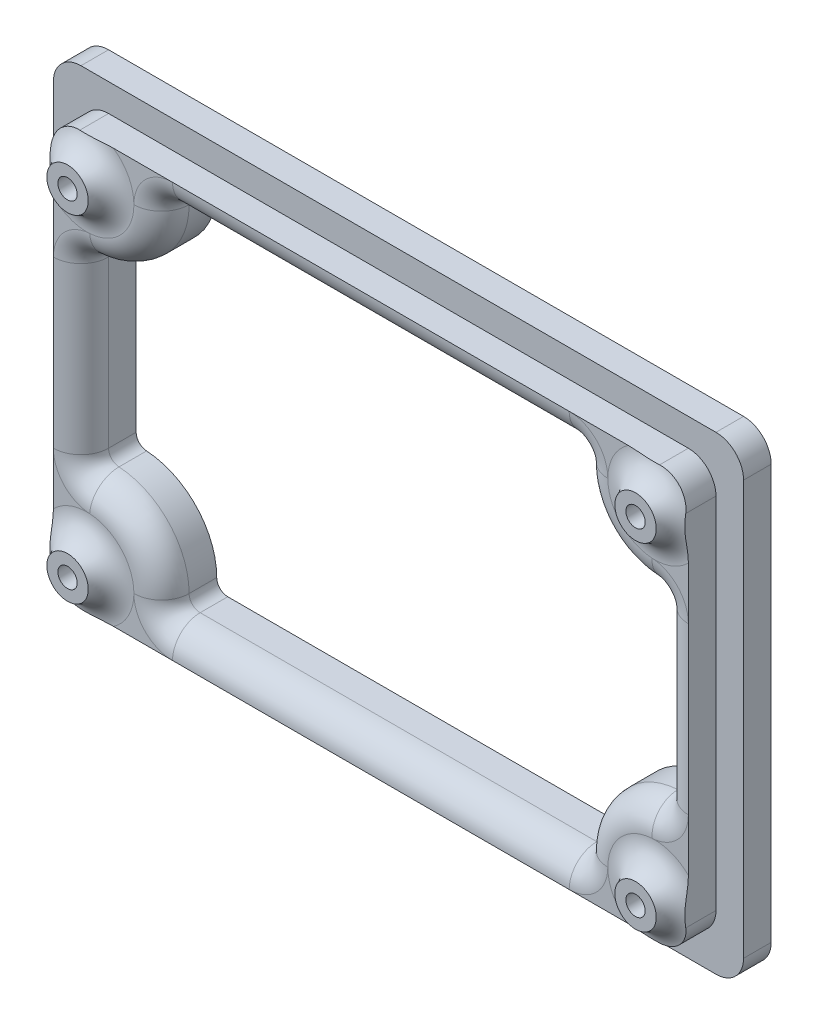
SolidWorks part; units mm, degrees
ref_plane "Ebene vorne" through (0, 0, 0) normal (0, 0, 1) x (1, 0, 0)
ref_plane "Ebene oben" through (0, 0, 0) normal (0, 1, 0) x (1, 0, 0)
ref_plane "Ebene rechts" through (0, 0, 0) normal (1, 0, 0) x (0, 0, -1)
sketch "Skizze1" plane through (0, 0, 0) normal (0, 0, 1) x (1, 0, 0)
  line L0 (-57.5, 75) -> (-57.5, 0) construction
  line L1 (0, 0) -> (-115, 0)
  line L2 (0, 0) -> (0, 75)
  line L3 (0, 75) -> (-115, 75)
  line L4 (-115, 0) -> (-115, 75)
  line L5 (-115, 37.5) -> (0, 37.5) construction
  circle A0 centre (-108.935, 67.98) radius 1.75
  circle A1 centre (-6.065, 67.98) radius 1.75
  circle A2 centre (-6.065, 7.02) radius 1.75
  circle A3 centre (-108.935, 7.02) radius 1.75
  dimension "D3" = 3.5
  dimension "D1" = 75
  dimension "D2" = 115
  dimension "D4" = 102.87
  dimension "D5" = 60.96
extrude "Aufsatz-Linear austragen1" add sketch "Skizze1" along normal blind 5
sketch "Skizze2" plane through (0, 0, 5) normal (0, 0, 1) x (1, 0, 0)
  line L0 (-57.5, 75) -> (-57.5, 0) construction
  line L1 (0, 75) -> (-115, 75) construction
  line L2 (-115, 0) -> (0, 0) construction
  line L3 (-115, 37.5) -> (0, 37.5) construction
  line L4 (-115, 75) -> (-115, 0) construction
  line L5 (0, 0) -> (0, 75) construction
  circle A11 centre (-108.935, 67.98) radius 1.75 construction
  circle A12 centre (-108.935, 67.98) radius 3.75
  circle A13 centre (-108.935, 67.98) radius 3.75
  circle A14 centre (-108.935, 67.98) radius 1.75
  circle A15 centre (-6.065, 67.98) radius 1.75
  circle A16 centre (-6.065, 67.98) radius 3.75
  circle A17 centre (-108.935, 7.02) radius 1.75
  circle A18 centre (-108.935, 7.02) radius 3.75
  circle A19 centre (-6.065, 7.02) radius 3.75
  circle A20 centre (-6.065, 7.02) radius 1.75
  dimension "D1" = 2
extrude "Aufsatz-Linear austragen2" add sketch "Skizze2" along normal blind 3.5
sketch "Skizze3" plane through (0, 0, 0) normal (0, 0, -1) x (-1, 0, 0)
  line L24 (-5, 80) -> (-5, -5)
  line L25 (-5, -5) -> (120, -5)
  line L30 (120, -5) -> (120, 80)
  line L31 (120, 80) -> (-5, 80)
  line L32 (-5, 80) -> (-5, -5)
  line L33 (-5, -5) -> (120, -5)
  line L34 (120, -5) -> (120, 80)
  line L35 (120, 80) -> (-5, 80)
  dimension "D1" = 5
extrude "Aufsatz-Linear austragen4" add sketch "Skizze3" along normal blind 5 contours L32 L33 L34 L35
fillet "Verrundung1" radius 5 4 edges at (-115, 75, 2.5) (-115, 0, 2.5) (0, 0, 2.5) (0, 75, 2.5)
fillet "Verrundung2" radius 5 4 edges at (5, -5, -2.5) (5, 80, -2.5) (-120, 80, -2.5) (-120, -5, -2.5)
fillet "Verrundung3" radius 5 4 edges at (-105.185, 67.98, 5) (-9.815, 67.98, 5) (-2.315, 7.02, 5) (-112.685, 7.02, 5)
sketch "Skizze4" plane through (0, 0, 8.5) normal (0, 0, 1) x (1, 0, 0)
  circle A0 centre (-108.935, 7.02) radius 1.75 construction
  circle A1 centre (-6.065, 7.02) radius 1.75 construction
  circle A2 centre (-6.065, 67.98) radius 1.75 construction
  circle A3 centre (-108.935, 67.98) radius 1.75 construction
  circle A4 centre (-108.935, 7.02) radius 1.75
  circle A5 centre (-6.065, 7.02) radius 1.75
  circle A6 centre (-6.065, 67.98) radius 1.75
  circle A7 centre (-108.935, 67.98) radius 1.75
extrude "Schnitt-Linear austragen1" cut sketch "Skizze4" against normal through all
sketch "Skizze5" plane through (0, 0, 5) normal (0, 0, 1) x (1, 0, 0)
  line L8 (-19.4329, 70) -> (-95.5671, 70)
  line L9 (-110, 54.5023) -> (-110, 20.4977)
  line L10 (-95.5671, 5) -> (-19.4329, 5)
  line L11 (-5, 20.4977) -> (-5, 54.5023)
  line L12 (-21.5847, 70) -> (-93.4153, 70)
  line L13 (-110, 52.4885) -> (-110, 22.5115)
  line L14 (-93.4153, 5) -> (-21.5847, 5)
  line L15 (-5, 22.5115) -> (-5, 52.4885)
  arc A4 (-110, 22.5115) -> (-108.1205, 20.5151) centre (-108, 22.5115) ccw
  arc A5 (-95.4153, 7.0026) -> (-93.4153, 5) centre (-93.4153, 7) ccw
  arc A6 (-21.5847, 5) -> (-19.5847, 7.0026) centre (-21.5847, 7) ccw
  arc A7 (-6.8795, 20.5151) -> (-5, 22.5115) centre (-7, 22.5115) ccw
  arc A8 (-110, 54.5023) -> (-95.5671, 70) centre (-108.935, 67.98) ccw
  arc A9 (-95.5671, 5) -> (-110, 20.4977) centre (-108.935, 7.02) ccw
  arc A10 (-5, 20.4977) -> (-19.4329, 5) centre (-6.065, 7.02) ccw
  arc A11 (-19.4329, 70) -> (-5, 54.5023) centre (-6.065, 67.98) ccw
  arc A12 (-108.1205, 54.4849) -> (-95.4153, 67.9974) centre (-108.935, 67.98) ccw
  arc A13 (-95.4153, 7.0026) -> (-108.1205, 20.5151) centre (-108.935, 7.02) ccw
  arc A14 (-6.8795, 20.5151) -> (-19.5847, 7.0026) centre (-6.065, 7.02) ccw
  arc A15 (-19.5847, 67.9974) -> (-6.8795, 54.4849) centre (-6.065, 67.98) ccw
  arc A16 (-5, 52.4885) -> (-6.8795, 54.4849) centre (-7, 52.4885) ccw
  arc A17 (-19.5847, 67.9974) -> (-21.5847, 70) centre (-21.5847, 68) ccw
  arc A18 (-93.4153, 70) -> (-95.4153, 67.9974) centre (-93.4153, 68) ccw
  arc A19 (-108.1205, 54.4849) -> (-110, 52.4885) centre (-108, 52.4885) ccw
  point P0 (0, 0)
  dimension "D2" = 2
  dimension "D1" = 5
extrude "Schnitt-Linear austragen2" cut sketch "Skizze5" against normal through all
fillet "Verrundung5" radius 5 16 edges at (-20.1696, 69.4133, 5) (-15.9146, 58.7189, 5) (-5.5438, 53.8594, 5) (-5, 37.5, 5) (-5.5438, 21.1406, 5) (-15.9146, 16.2811, 5) (-20.1696, 5.5867, 5) (-57.5, 5, 5) (-94.8304, 5.5867, 5) (-99.0854, 16.2811, 5) (-109.4562, 21.1406, 5) (-110, 37.5, 5) (-109.4562, 53.8594, 5) (-99.0854, 58.7189, 5) (-94.8304, 69.4133, 5) (-57.5, 70, 5)
sketch "Skizze6" plane through (0, 0, -5) normal (0, 0, -1) x (-1, 0, 0)
  circle A1 centre (108.935, 7.02) radius 5
  circle A2 centre (6.065, 7.02) radius 5
  circle A3 centre (108.935, 67.98) radius 5
  circle A4 centre (6.065, 67.98) radius 5
  dimension "D1" = 10
  dimension "D2" = 10
  dimension "D3" = 10
  dimension "D4" = 10
extrude "Schnitt-Linear austragen3" cut sketch "Skizze6" against normal blind 8
